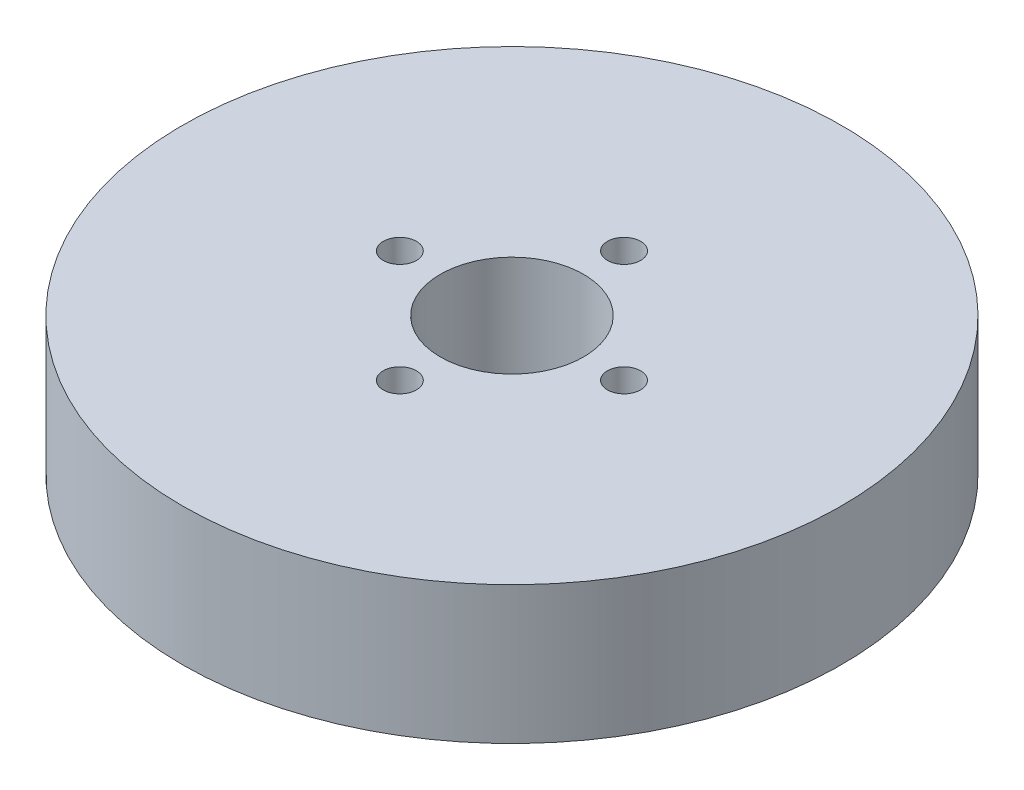
SolidWorks part; units mm, degrees
ref_plane "Front Plane" through (0, 0, 0) normal (0, 0, 1) x (1, 0, 0)
ref_plane "Top Plane" through (0, 0, 0) normal (0, 1, 0) x (1, 0, 0)
ref_plane "Right Plane" through (0, 0, 0) normal (1, 0, 0) x (0, 0, -1)
sketch "Sketch1" plane through (0, 0, 0) normal (0, 1, 0) x (1, 0, 0)
  circle A0 centre (0, 0) radius 57.5
  dimension "FLANGE_OD" = 115
extrude "Boss-Extrude1" add sketch "Sketch1" along normal blind 24
sketch "Sketch2" plane through (0, 0, 0) normal (0, 1, 0) x (1, 0, 0)
  circle A0 centre (0, 0) radius 12.5
  dimension "BORE_D" = 25
extrude "Cut-Extrude1" cut sketch "Sketch2" along normal through all
sketch "Sketch3" plane through (0, 24, 0) normal (0, 1, 0) x (1, 0, 0)
  circle A0 centre (0, 0) radius 19.5589 construction
  circle A1 centre (-19.5589, 0) radius 2.8969
  dimension "BOLT_D" = 5.7937
  dimension "BOLT_PCD" = 39.1179
extrude "Cut-Extrude2" cut sketch "Sketch3" against normal blind 19.0983
pattern_circular "CirPattern1" count 4 over 360 about axis through (0, 0, 0) along (0, 1, 0) of "Cut-Extrude2"
